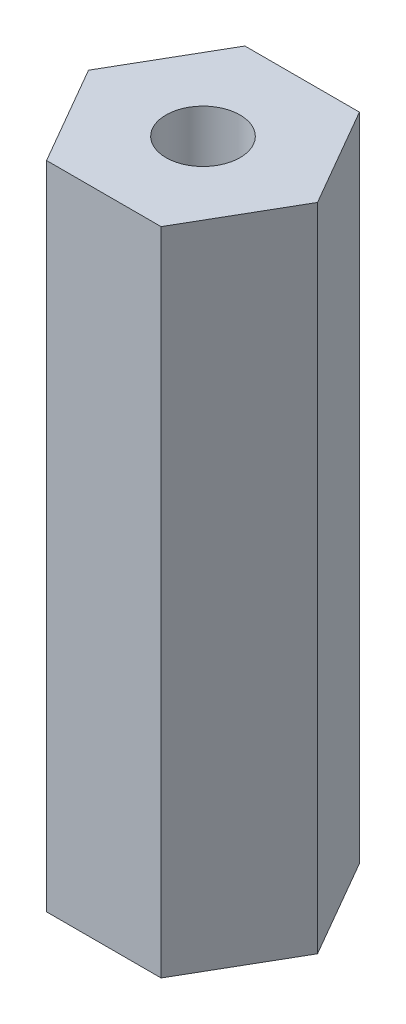
SolidWorks part; units mm, degrees
material "Brass"
ref_plane "Front Plane" through (0, 0, 0) normal (0, 0, 1) x (1, 0, 0)
ref_plane "Top Plane" through (0, 0, 0) normal (0, 1, 0) x (1, 0, 0)
ref_plane "Right Plane" through (0, 0, 0) normal (1, 0, 0) x (0, 0, -1)
sketch "Sketch1" plane through (0, 0, 0) normal (0, 1, 0) x (1, 0, 0)
  line L1 (4.3994, 0) -> (2.1997, 3.81)
  line L2 (2.1997, 3.81) -> (-2.1997, 3.81)
  line L3 (-2.1997, 3.81) -> (-4.3994, 0)
  line L4 (-4.3994, 0) -> (-2.1997, -3.81)
  line L5 (-2.1997, -3.81) -> (2.1997, -3.81)
  line L6 (2.1997, -3.81) -> (4.3994, 0)
  circle A0 centre (0, 0) radius 3.81 construction
extrude "Boss-Extrude1" add sketch "Sketch1" along normal blind 25
sketch "Sketch2" plane through (0, 25, 0) normal (0, 1, 0) x (1, 0, 0)
  circle A0 centre (0, 0) radius 1.4224
  dimension "D1" = 2.8448
extrude "Cut-Extrude1" cut sketch "Sketch2" against normal through all
equation "\"D1@Boss-Extrude1\"=25mm"
